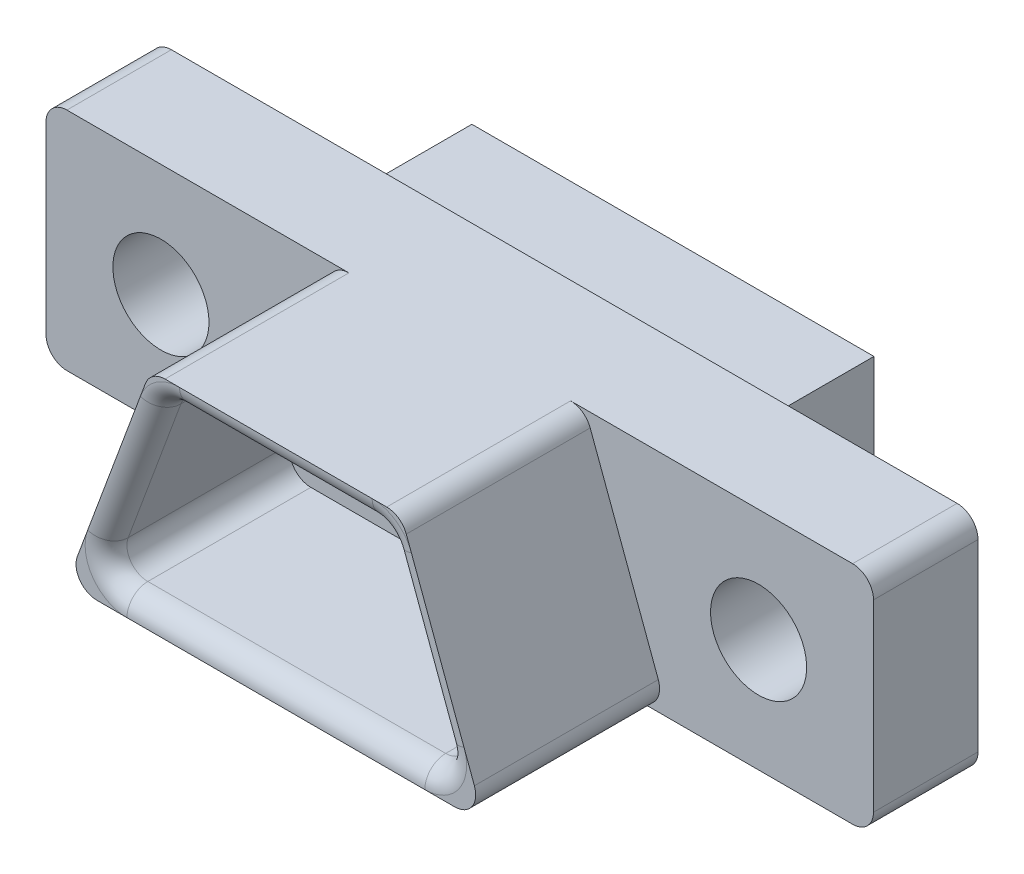
SolidWorks part; units mm, degrees
ref_plane "前视基准面" through (0, 0, 0) normal (0, 0, 1) x (1, 0, 0)
ref_plane "上视基准面" through (0, 0, 0) normal (0, 1, 0) x (1, 0, 0)
ref_plane "右视基准面" through (0, 0, 0) normal (1, 0, 0) x (0, 0, -1)
sketch "草图1" plane through (0, 0, 0) normal (0, 0, 1) x (1, 0, 0)
  line L0 (0, -5.928) -> (0, 7.248) construction
  line L1 (-9.9, -2.7) -> (9.9, -2.7)
  line L2 (-9.9, -2.7) -> (-9.9, 2.7)
  line L3 (-9.9, 2.7) -> (9.9, 2.7)
  line L4 (9.9, -2.7) -> (9.9, 2.7)
  line L5 (-12.6323, 0) -> (15.3794, 0) construction
  circle A0 centre (-7.15, 0) radius 1.15
  circle A1 centre (7.15, 0) radius 1.15
  point P4 (0, 2.7)
  dimension "D1" = 7.15
  dimension "D2" = 0
  dimension "D3" = 0
extrude "凸台-拉伸1" add sketch "草图1" along normal blind 2.5
fillet "圆角1" radius 0.5 1 edges at (-9.9, 2.7, 1.25)
fillet "圆角2" radius 0.5 3 edges at (-9.9, -2.7, 1.25) (9.9, -2.7, 1.25) (9.9, 2.7, 1.25)
sketch "草图3" plane through (0, 0, 0) normal (0, 0, -1) x (-1, 0, 0)
  line L1 (-4.81, 2.15) -> (4.81, 2.15)
  line L2 (-4.81, 2.15) -> (-4.81, -2.15)
  line L3 (-4.81, -2.15) -> (4.81, -2.15)
  line L4 (4.81, 2.15) -> (4.81, -2.15)
  dimension "D1" = 9.62
  dimension "D2" = 4.3
  dimension "D3" = 4.81
  dimension "D4" = 2.15
extrude "凸台-拉伸2" add sketch "草图3" along normal blind 2.6
sketch "草图4" plane through (0, 0, -2.6) normal (0, 0, -1) x (-1, 0, 0)
  line L0 (0, 3.2827) -> (0, -3.6632) construction
  circle A1 centre (-1.905, 0.55) radius 0.31
  circle A2 centre (-0.635, 0.55) radius 0.31
  circle A3 centre (0.635, 0.55) radius 0.31
  circle A4 centre (1.905, 0.55) radius 0.31
  circle A11 centre (-2.54, -0.55) radius 0.31
  circle A12 centre (-1.27, -0.55) radius 0.31
  circle A13 centre (0, -0.55) radius 0.31
  circle A14 centre (1.27, -0.55) radius 0.31
  circle A15 centre (2.54, -0.55) radius 0.31
  dimension "D1" = 4
extrude "切除-拉伸1" cut sketch "草图4" against normal blind 4.5
sketch "草图5" plane through (0, 0, 2.5) normal (0, 0, 1) x (1, 0, 0)
  line L0 (-2.652, 2.7) -> (2.652, 2.7)
  line L1 (-4.2816, -2.7) -> (4.2816, -2.7)
  line L2 (-3.1209, 2.3737) -> (-4.7505, -2.0263)
  line L4 (3.1209, 2.3737) -> (4.7505, -2.0263)
  line L6 (-2.304, 2.2) -> (2.304, 2.2)
  line L7 (2.7729, 1.8737) -> (4.0321, -1.5263)
  line L8 (-3.5632, -2.2) -> (3.5632, -2.2)
  line L9 (-2.7729, 1.8737) -> (-4.0321, -1.5263)
  line L10 (-5, -2.7) -> (5, -2.7) construction
  line L11 (-3, 2.7) -> (-5, -2.7) construction
  line L12 (-4.2816, -2.2) -> (4.2816, -2.2) construction
  line L13 (-2.652, 2.2) -> (-4.2816, -2.2) construction
  line L14 (3, 2.7) -> (5, -2.7) construction
  line L15 (2.652, 2.2) -> (4.2816, -2.2) construction
  line L16 (-3, 2.7) -> (3, 2.7) construction
  line L17 (-2.652, 2.2) -> (2.652, 2.2) construction
  arc A0 (-4.2816, -2.7) -> (-4.7505, -2.0263) centre (-4.2816, -2.2) cw
  arc A1 (-3.5632, -2.2) -> (-4.0321, -1.5263) centre (-3.5632, -1.7) cw
  arc A2 (4.2816, -2.7) -> (4.7505, -2.0263) centre (4.2816, -2.2) ccw
  arc A3 (3.5632, -2.2) -> (4.0321, -1.5263) centre (3.5632, -1.7) ccw
  arc A4 (3.1209, 2.3737) -> (2.652, 2.7) centre (2.652, 2.2) ccw
  arc A5 (2.304, 2.2) -> (2.7729, 1.8737) centre (2.304, 1.7) cw
  arc A6 (-2.304, 2.2) -> (-2.7729, 1.8737) centre (-2.304, 1.7) ccw
  arc A7 (-2.652, 2.7) -> (-3.1209, 2.3737) centre (-2.652, 2.2) ccw
  point P4 (0, -2.7)
  dimension "D1" = 0.5
  dimension "D2" = 0.5
  dimension "D3" = 0
extrude "凸台-拉伸3" add sketch "草图5" along normal blind 4.4
fillet "圆角3" radius 0.5 8 edges at (-2.5896, 2.1104, 6.9) (0, 2.2, 6.9) (2.5896, 2.1104, 6.9) (3.4025, 0.1737, 6.9) (3.9736, -1.9856, 6.9) (0, -2.2, 6.9) (-3.9736, -1.9856, 6.9) (-3.4025, 0.1737, 6.9)
equation "\"23..6mm\"=11.36"
